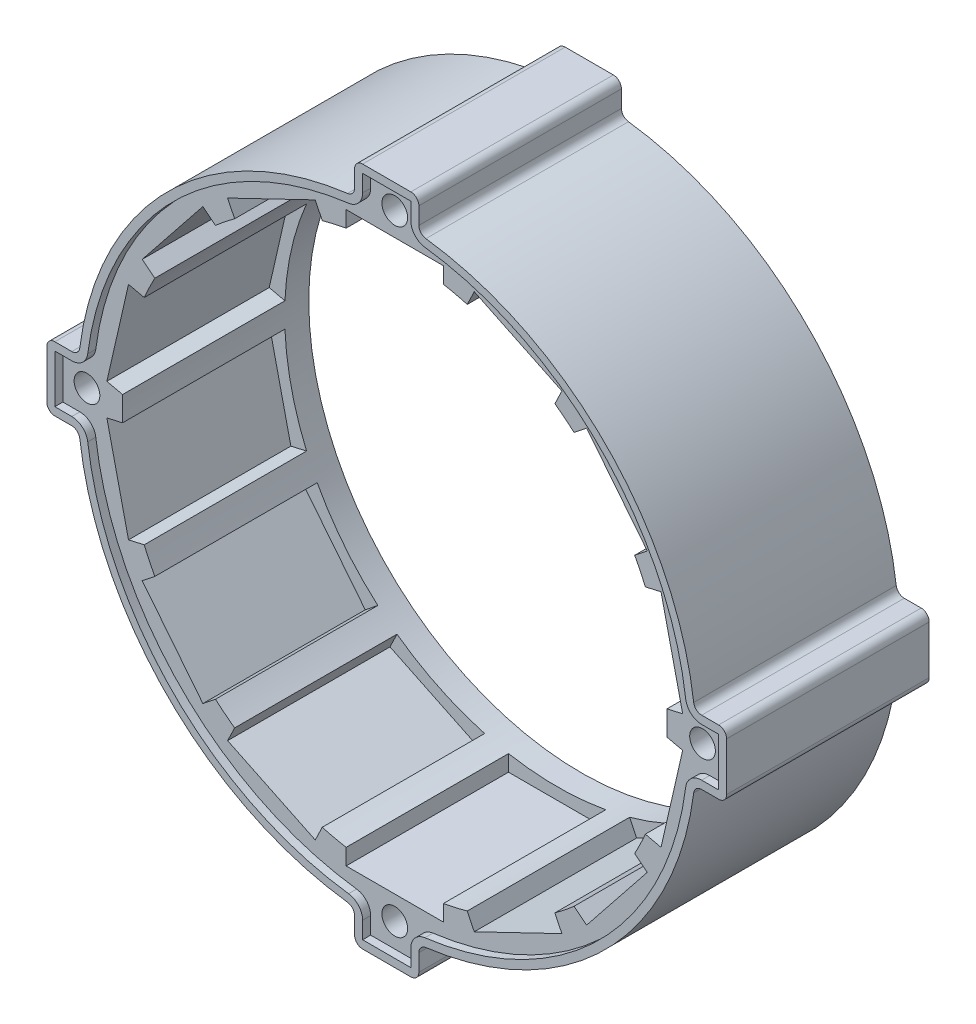
SolidWorks part; units mm, degrees
ref_plane "正面" through (0, 0, 0) normal (0, 0, 1) x (1, 0, 0)
ref_plane "平面" through (0, 0, 0) normal (0, 1, 0) x (1, 0, 0)
ref_plane "右側面" through (0, 0, 0) normal (1, 0, 0) x (0, 0, -1)
sketch "ｽｹｯﾁ1" plane through (0, 0, 0) normal (0, 0, 1) x (1, 0, 0)
  line L0 (38.8333, 0) -> (34.9876, 16.8491) construction
  line L1 (33.7047, 0) -> (30.3669, 14.6239)
  line L2 (30.3669, 14.6239) -> (21.0145, 26.3514)
  line L3 (21.0145, 26.3514) -> (7.5, 32.8596)
  line L4 (7.5, 32.8596) -> (-7.5, 32.8596)
  line L5 (-7.5, 32.8596) -> (-21.0145, 26.3514)
  line L6 (-21.0145, 26.3514) -> (-30.3669, 14.6239)
  line L7 (-30.3669, 14.6239) -> (-33.7047, 0)
  line L8 (-33.7047, 0) -> (-30.3669, -14.6239)
  line L9 (-30.3669, -14.6239) -> (-21.0145, -26.3514)
  line L10 (-21.0145, -26.3514) -> (-7.5, -32.8596)
  line L11 (-7.5, -32.8596) -> (7.5, -32.8596)
  line L12 (7.5, -32.8596) -> (21.0145, -26.3514)
  line L13 (21.0145, -26.3514) -> (30.3669, -14.6239)
  line L14 (30.3669, -14.6239) -> (33.7047, 0)
  line L15 (34.9876, 16.8491) -> (24.2122, 30.3611) construction
  line L16 (24.2122, 30.3611) -> (8.6412, 37.8596) construction
  line L17 (8.6412, 37.8596) -> (-8.6412, 37.8596) construction
  line L18 (-8.6412, 37.8596) -> (-24.2122, 30.3611) construction
  line L19 (-24.2122, 30.3611) -> (-34.9876, 16.8491) construction
  line L20 (-34.9876, 16.8491) -> (-38.8333, 0) construction
  line L21 (-38.8333, 0) -> (-34.9876, -16.8491) construction
  line L22 (-34.9876, -16.8491) -> (-24.2122, -30.3611) construction
  line L23 (-24.2122, -30.3611) -> (-8.6412, -37.8596) construction
  line L24 (-8.6412, -37.8596) -> (8.6412, -37.8596) construction
  line L25 (8.6412, -37.8596) -> (24.2122, -30.3611) construction
  line L26 (24.2122, -30.3611) -> (34.9876, -16.8491) construction
  line L27 (34.9876, -16.8491) -> (38.8333, 0) construction
  circle A0 centre (0, 0) radius 32.8596 construction
  circle A1 centre (0, 0) radius 38.5
  dimension "D3" = 77
  dimension "D1" = 15
  dimension "D2" = 5
extrude "ﾎﾞｽ - 押し出し1" add sketch "ｽｹｯﾁ1" along normal blind 20.2
ref_axis "軸1" through (0, 0, 0) along (0, 0, 1)
sketch "ｽｹｯﾁ3" plane through (0, 0, 20.2) normal (0, 0, 1) x (1, 0, 0)
  line L0 (0, 0) -> (0, 33.0954) construction
  line L1 (7.5, 32.8596) -> (-7.5, 32.8596) construction
  line L2 (-6.05, 35.3596) -> (6.05, 35.3596)
  line L3 (-6.05, 35.3596) -> (-6.05, 32.8596)
  line L4 (-6.05, 32.8596) -> (6.05, 32.8596)
  line L5 (6.05, 35.3596) -> (6.05, 32.8596)
  line L6 (-6.05, 35.3596) -> (6.05, 32.8596) construction
  line L7 (-6.05, 32.8596) -> (6.05, 35.3596) construction
  point P3 (0, 34.1096)
  dimension "D1" = 2.5
  dimension "D2" = 12.1
extrude "ｶｯﾄ - 押し出し2" cut sketch "ｽｹｯﾁ3" against normal through all
pattern_circular "円形ﾊﾟﾀｰﾝ2" count 14 over 360 about axis through (0, 0, 0) along (0, 0, 1) of "ｶｯﾄ - 押し出し2"
sketch "ｽｹｯﾁ5" plane through (0, 0, 0) normal (0, 0, -1) x (-1, 0, 0)
  circle A0 centre (0, 0) radius 33.9
  circle A1 centre (0, 0) radius 38.5
  circle A2 centre (0, 0) radius 38.5
  dimension "D1" = 0
  dimension "D2" = 4.6
extrude "ﾎﾞｽ - 押し出し2" add sketch "ｽｹｯﾁ5" along normal blind 3
sketch "ｽｹｯﾁ6" plane through (0, 0, -3) normal (0, 0, -1) x (-1, 0, 0)
  circle A0 centre (0, 0) radius 33.9 construction
  circle A1 centre (0, 0) radius 33.9
extrude "ｶｯﾄ - 押し出し3" cut sketch "ｽｹｯﾁ6" against normal through all
sketch "ｽｹｯﾁ7" plane through (0, 0, -3) normal (0, 0, -1) x (-1, 0, 0)
  line L0 (0, 0) -> (0, 38.5) construction
  line L1 (4, 42.2916) -> (-4, 42.2916)
  line L2 (-4, 42.2916) -> (-4, 38.2916)
  line L3 (4, 42.2916) -> (4, 38.2916)
  circle A0 centre (0, 0) radius 38.5 construction
  circle A2 centre (0, 0) radius 38.5
  arc A3 (4, 38.2916) -> (-4, 38.2916) centre (0, 0) ccw
  point P10 (0, 42.2916)
  dimension "D2" = 8
  dimension "D3" = 4
  dimension "D1" = 0
extrude "ﾎﾞｽ - 押し出し3" add sketch "ｽｹｯﾁ7" against normal up to surface (23.2 mm away) up to face at (0, 0, 20.2)
pattern_circular "円形ﾊﾟﾀｰﾝ3" count 4 over 360 about axis through (0, 0, 0) along (0, 0, 1) of "ﾎﾞｽ - 押し出し3"
sketch "ｽｹｯﾁ8" plane through (0, 0, -3) normal (0, 0, -1) x (-1, 0, 0)
  line L0 (4, 42.2916) -> (-4, 42.2916) construction
  line L1 (0, 0) -> (0, 38.2916) construction
  circle A0 centre (0, 38.2916) radius 1.6
  circle A4 centre (38.2916, 0) radius 1.6
  circle A5 centre (0, -38.2916) radius 1.6
  circle A6 centre (-38.2916, 0) radius 1.6
  point P13 (-0.4544, 0.4544)
  point P15 (0, 0)
  dimension "D1" = 3.2
  dimension "D2" = 4
  dimension "D3" = 4
extrude "ｶｯﾄ - 押し出し4" cut sketch "ｽｹｯﾁ8" against normal through all
fillet "ﾌｨﾚｯﾄ1" radius 1 16 edges at (4, -38.2916, 8.6) (4, -42.2916, 8.6) (-4, -42.2916, 8.6) (-4, -38.2916, 8.6) (-38.2916, -4, 8.6) (-42.2916, -4, 8.6) (-42.2916, 4, 8.6) (-38.2916, 4, 8.6) (-4, 38.2916, 8.6) (-4, 42.2916, 8.6) (4, 42.2916, 8.6) (4, 38.2916, 8.6) (38.2916, 4, 8.6) (42.2916, 4, 8.6) (42.2916, -4, 8.6) (38.2916, -4, 8.6)
sketch "ｽｹｯﾁ9" plane through (0, 0, -3) normal (0, 0, -1) x (-1, 0, 0)
  line L0 (-3, -39.1823) -> (-3, -41.2916)
  line L1 (-3, -41.2916) -> (3, -41.2916)
  line L2 (3, -41.2916) -> (3, -39.1823)
  line L3 (39.1823, -3) -> (41.2916, -3)
  line L4 (41.2916, -3) -> (41.2916, 3)
  line L5 (41.2916, 3) -> (39.1823, 3)
  line L6 (3, 39.1823) -> (3, 41.2916)
  line L7 (3, 41.2916) -> (-3, 41.2916)
  line L8 (-3, 41.2916) -> (-3, 39.1823)
  line L9 (-39.1823, 3) -> (-41.2916, 3)
  line L10 (-41.2916, 3) -> (-41.2916, -3)
  line L11 (-41.2916, -3) -> (-39.1823, -3)
  line L12 (-4, -39.1823) -> (-4, -41.2916)
  line L13 (-3, -42.2916) -> (3, -42.2916)
  line L14 (4, -41.2916) -> (4, -39.1823)
  line L15 (39.1823, -4) -> (41.2916, -4)
  line L16 (42.2916, -3) -> (42.2916, 3)
  line L17 (41.2916, 4) -> (39.1823, 4)
  line L18 (4, 39.1823) -> (4, 41.2916)
  line L19 (3, 42.2916) -> (-3, 42.2916)
  line L20 (-4, 41.2916) -> (-4, 39.1823)
  line L21 (-39.1823, 4) -> (-41.2916, 4)
  line L22 (-42.2916, 3) -> (-42.2916, -3)
  line L23 (-41.2916, -4) -> (-39.1823, -4)
  line L24 (-4, -39.1823) -> (-4, -41.2916)
  line L25 (-3, -42.2916) -> (3, -42.2916)
  line L26 (4, -41.2916) -> (4, -39.1823)
  line L27 (39.1823, -4) -> (41.2916, -4)
  line L28 (42.2916, -3) -> (42.2916, 3)
  line L29 (41.2916, 4) -> (39.1823, 4)
  line L30 (4, 39.1823) -> (4, 41.2916)
  line L31 (3, 42.2916) -> (-3, 42.2916)
  line L32 (-4, 41.2916) -> (-4, 39.1823)
  line L33 (-39.1823, 4) -> (-41.2916, 4)
  line L34 (-42.2916, 3) -> (-42.2916, -3)
  line L35 (-41.2916, -4) -> (-39.1823, -4)
  arc A0 (-3, -41.2916) -> (-3, -41.2916) centre (-3, -41.2916) ccw
  arc A1 (3, -41.2916) -> (3, -41.2916) centre (3, -41.2916) ccw
  arc A2 (4.7468, -37.1984) -> (3, -39.1823) centre (5, -39.1823) ccw
  arc A3 (4.7468, -37.1984) -> (37.1984, -4.7468) centre (0, 0) ccw
  arc A4 (39.1823, -3) -> (37.1984, -4.7468) centre (39.1823, -5) ccw
  arc A5 (41.2916, -3) -> (41.2916, -3) centre (41.2916, -3) ccw
  arc A6 (41.2916, 3) -> (41.2916, 3) centre (41.2916, 3) ccw
  arc A7 (37.1984, 4.7468) -> (39.1823, 3) centre (39.1823, 5) ccw
  arc A8 (37.1984, 4.7468) -> (4.7468, 37.1984) centre (0, 0) ccw
  arc A9 (3, 39.1823) -> (4.7468, 37.1984) centre (5, 39.1823) ccw
  arc A10 (3, 41.2916) -> (3, 41.2916) centre (3, 41.2916) ccw
  arc A11 (-3, 41.2916) -> (-3, 41.2916) centre (-3, 41.2916) ccw
  arc A12 (-4.7468, 37.1984) -> (-3, 39.1823) centre (-5, 39.1823) ccw
  arc A13 (-4.7468, 37.1984) -> (-37.1984, 4.7468) centre (0, 0) ccw
  arc A14 (-39.1823, 3) -> (-37.1984, 4.7468) centre (-39.1823, 5) ccw
  arc A15 (-41.2916, 3) -> (-41.2916, 3) centre (-41.2916, 3) ccw
  arc A16 (-41.2916, -3) -> (-41.2916, -3) centre (-41.2916, -3) ccw
  arc A17 (-37.1984, -4.7468) -> (-39.1823, -3) centre (-39.1823, -5) ccw
  arc A18 (-37.1984, -4.7468) -> (-4.7468, -37.1984) centre (0, 0) ccw
  arc A19 (-3, -39.1823) -> (-4.7468, -37.1984) centre (-5, -39.1823) ccw
  arc A20 (-4, -41.2916) -> (-3, -42.2916) centre (-3, -41.2916) ccw
  arc A21 (3, -42.2916) -> (4, -41.2916) centre (3, -41.2916) ccw
  arc A22 (4.8734, -38.1903) -> (4, -39.1823) centre (5, -39.1823) ccw
  arc A23 (4.8734, -38.1903) -> (38.1903, -4.8734) centre (0, 0) ccw
  arc A24 (39.1823, -4) -> (38.1903, -4.8734) centre (39.1823, -5) ccw
  arc A25 (41.2916, -4) -> (42.2916, -3) centre (41.2916, -3) ccw
  arc A26 (42.2916, 3) -> (41.2916, 4) centre (41.2916, 3) ccw
  arc A27 (38.1903, 4.8734) -> (39.1823, 4) centre (39.1823, 5) ccw
  arc A28 (38.1903, 4.8734) -> (4.8734, 38.1903) centre (0, 0) ccw
  arc A29 (4, 39.1823) -> (4.8734, 38.1903) centre (5, 39.1823) ccw
  arc A30 (4, 41.2916) -> (3, 42.2916) centre (3, 41.2916) ccw
  arc A31 (-3, 42.2916) -> (-4, 41.2916) centre (-3, 41.2916) ccw
  arc A32 (-4.8734, 38.1903) -> (-4, 39.1823) centre (-5, 39.1823) ccw
  arc A33 (-4.8734, 38.1903) -> (-38.1903, 4.8734) centre (0, 0) ccw
  arc A34 (-39.1823, 4) -> (-38.1903, 4.8734) centre (-39.1823, 5) ccw
  arc A35 (-41.2916, 4) -> (-42.2916, 3) centre (-41.2916, 3) ccw
  arc A36 (-42.2916, -3) -> (-41.2916, -4) centre (-41.2916, -3) ccw
  arc A37 (-38.1903, -4.8734) -> (-39.1823, -4) centre (-39.1823, -5) ccw
  arc A38 (-38.1903, -4.8734) -> (-4.8734, -38.1903) centre (0, 0) ccw
  arc A39 (-4, -39.1823) -> (-4.8734, -38.1903) centre (-5, -39.1823) ccw
  arc A40 (-4, -41.2916) -> (-3, -42.2916) centre (-3, -41.2916) ccw
  arc A41 (3, -42.2916) -> (4, -41.2916) centre (3, -41.2916) ccw
  arc A42 (4.8734, -38.1903) -> (4, -39.1823) centre (5, -39.1823) ccw
  arc A43 (4.8734, -38.1903) -> (38.1903, -4.8734) centre (0, 0) ccw
  arc A44 (39.1823, -4) -> (38.1903, -4.8734) centre (39.1823, -5) ccw
  arc A45 (41.2916, -4) -> (42.2916, -3) centre (41.2916, -3) ccw
  arc A46 (42.2916, 3) -> (41.2916, 4) centre (41.2916, 3) ccw
  arc A47 (38.1903, 4.8734) -> (39.1823, 4) centre (39.1823, 5) ccw
  arc A48 (38.1903, 4.8734) -> (4.8734, 38.1903) centre (0, 0) ccw
  arc A49 (4, 39.1823) -> (4.8734, 38.1903) centre (5, 39.1823) ccw
  arc A50 (4, 41.2916) -> (3, 42.2916) centre (3, 41.2916) ccw
  arc A51 (-3, 42.2916) -> (-4, 41.2916) centre (-3, 41.2916) ccw
  arc A52 (-4.8734, 38.1903) -> (-4, 39.1823) centre (-5, 39.1823) ccw
  arc A53 (-4.8734, 38.1903) -> (-38.1903, 4.8734) centre (0, 0) ccw
  arc A54 (-39.1823, 4) -> (-38.1903, 4.8734) centre (-39.1823, 5) ccw
  arc A55 (-41.2916, 4) -> (-42.2916, 3) centre (-41.2916, 3) ccw
  arc A56 (-42.2916, -3) -> (-41.2916, -4) centre (-41.2916, -3) ccw
  arc A57 (-38.1903, -4.8734) -> (-39.1823, -4) centre (-39.1823, -5) ccw
  arc A58 (-38.1903, -4.8734) -> (-4.8734, -38.1903) centre (0, 0) ccw
  arc A59 (-4, -39.1823) -> (-4.8734, -38.1903) centre (-5, -39.1823) ccw
  dimension "D1" = 0
  dimension "D2" = 1
extrude "ﾎﾞｽ - 押し出し4" add sketch "ｽｹｯﾁ9" along normal blind 1
sketch "ｽｹｯﾁ10" plane through (0, 0, 20.2) normal (0, 0, 1) x (1, 0, 0)
  line L0 (-3, -41.2916) -> (3, -41.2916)
  line L1 (3, -41.2916) -> (3, -39.1823)
  line L2 (39.1823, -3) -> (41.2916, -3)
  line L3 (41.2916, -3) -> (41.2916, 3)
  line L4 (41.2916, 3) -> (39.1823, 3)
  line L5 (3, 39.1823) -> (3, 41.2916)
  line L6 (3, 41.2916) -> (-3, 41.2916)
  line L7 (-3, 41.2916) -> (-3, 39.1823)
  line L8 (-39.1823, 3) -> (-41.2916, 3)
  line L9 (-41.2916, 3) -> (-41.2916, -3)
  line L10 (-41.2916, -3) -> (-39.1823, -3)
  line L11 (-3, -39.1823) -> (-3, -41.2916)
  line L12 (-3, -42.2916) -> (3, -42.2916)
  line L13 (4, -41.2916) -> (4, -39.1823)
  line L14 (39.1823, -4) -> (41.2916, -4)
  line L15 (42.2916, -3) -> (42.2916, 3)
  line L16 (41.2916, 4) -> (39.1823, 4)
  line L17 (4, 39.1823) -> (4, 41.2916)
  line L18 (3, 42.2916) -> (-3, 42.2916)
  line L19 (-4, 41.2916) -> (-4, 39.1823)
  line L20 (-39.1823, 4) -> (-41.2916, 4)
  line L21 (-42.2916, 3) -> (-42.2916, -3)
  line L22 (-41.2916, -4) -> (-39.1823, -4)
  line L23 (-4, -39.1823) -> (-4, -41.2916)
  line L24 (-3, -42.2916) -> (3, -42.2916)
  line L25 (4, -41.2916) -> (4, -39.1823)
  line L26 (39.1823, -4) -> (41.2916, -4)
  line L27 (42.2916, -3) -> (42.2916, 3)
  line L28 (41.2916, 4) -> (39.1823, 4)
  line L29 (4, 39.1823) -> (4, 41.2916)
  line L30 (3, 42.2916) -> (-3, 42.2916)
  line L31 (-4, 41.2916) -> (-4, 39.1823)
  line L32 (-39.1823, 4) -> (-41.2916, 4)
  line L33 (-42.2916, 3) -> (-42.2916, -3)
  line L34 (-41.2916, -4) -> (-39.1823, -4)
  line L35 (-4, -39.1823) -> (-4, -41.2916)
  arc A0 (3, -41.2916) -> (3, -41.2916) centre (3, -41.2916) ccw
  arc A1 (4.7468, -37.1984) -> (3, -39.1823) centre (5, -39.1823) ccw
  arc A2 (4.7468, -37.1984) -> (37.1984, -4.7468) centre (0, 0) ccw
  arc A3 (39.1823, -3) -> (37.1984, -4.7468) centre (39.1823, -5) ccw
  arc A4 (41.2916, -3) -> (41.2916, -3) centre (41.2916, -3) ccw
  arc A5 (41.2916, 3) -> (41.2916, 3) centre (41.2916, 3) ccw
  arc A6 (37.1984, 4.7468) -> (39.1823, 3) centre (39.1823, 5) ccw
  arc A7 (37.1984, 4.7468) -> (4.7468, 37.1984) centre (0, 0) ccw
  arc A8 (3, 39.1823) -> (4.7468, 37.1984) centre (5, 39.1823) ccw
  arc A9 (3, 41.2916) -> (3, 41.2916) centre (3, 41.2916) ccw
  arc A10 (-3, 41.2916) -> (-3, 41.2916) centre (-3, 41.2916) ccw
  arc A11 (-4.7468, 37.1984) -> (-3, 39.1823) centre (-5, 39.1823) ccw
  arc A12 (-4.7468, 37.1984) -> (-37.1984, 4.7468) centre (0, 0) ccw
  arc A13 (-39.1823, 3) -> (-37.1984, 4.7468) centre (-39.1823, 5) ccw
  arc A14 (-41.2916, 3) -> (-41.2916, 3) centre (-41.2916, 3) ccw
  arc A15 (-41.2916, -3) -> (-41.2916, -3) centre (-41.2916, -3) ccw
  arc A16 (-37.1984, -4.7468) -> (-39.1823, -3) centre (-39.1823, -5) ccw
  arc A17 (-37.1984, -4.7468) -> (-4.7468, -37.1984) centre (0, 0) ccw
  arc A18 (-3, -39.1823) -> (-4.7468, -37.1984) centre (-5, -39.1823) ccw
  arc A19 (-3, -41.2916) -> (-3, -41.2916) centre (-3, -41.2916) ccw
  arc A20 (3, -42.2916) -> (4, -41.2916) centre (3, -41.2916) ccw
  arc A21 (4.8734, -38.1903) -> (4, -39.1823) centre (5, -39.1823) ccw
  arc A22 (4.8734, -38.1903) -> (38.1903, -4.8734) centre (0, 0) ccw
  arc A23 (39.1823, -4) -> (38.1903, -4.8734) centre (39.1823, -5) ccw
  arc A24 (41.2916, -4) -> (42.2916, -3) centre (41.2916, -3) ccw
  arc A25 (42.2916, 3) -> (41.2916, 4) centre (41.2916, 3) ccw
  arc A26 (38.1903, 4.8734) -> (39.1823, 4) centre (39.1823, 5) ccw
  arc A27 (38.1903, 4.8734) -> (4.8734, 38.1903) centre (0, 0) ccw
  arc A28 (4, 39.1823) -> (4.8734, 38.1903) centre (5, 39.1823) ccw
  arc A29 (4, 41.2916) -> (3, 42.2916) centre (3, 41.2916) ccw
  arc A30 (-3, 42.2916) -> (-4, 41.2916) centre (-3, 41.2916) ccw
  arc A31 (-4.8734, 38.1903) -> (-4, 39.1823) centre (-5, 39.1823) ccw
  arc A32 (-4.8734, 38.1903) -> (-38.1903, 4.8734) centre (0, 0) ccw
  arc A33 (-39.1823, 4) -> (-38.1903, 4.8734) centre (-39.1823, 5) ccw
  arc A34 (-41.2916, 4) -> (-42.2916, 3) centre (-41.2916, 3) ccw
  arc A35 (-42.2916, -3) -> (-41.2916, -4) centre (-41.2916, -3) ccw
  arc A36 (-38.1903, -4.8734) -> (-39.1823, -4) centre (-39.1823, -5) ccw
  arc A37 (-38.1903, -4.8734) -> (-4.8734, -38.1903) centre (0, 0) ccw
  arc A38 (-4, -39.1823) -> (-4.8734, -38.1903) centre (-5, -39.1823) ccw
  arc A39 (-4, -41.2916) -> (-3, -42.2916) centre (-3, -41.2916) ccw
  arc A40 (3, -42.2916) -> (4, -41.2916) centre (3, -41.2916) ccw
  arc A41 (4.8734, -38.1903) -> (4, -39.1823) centre (5, -39.1823) ccw
  arc A42 (4.8734, -38.1903) -> (38.1903, -4.8734) centre (0, 0) ccw
  arc A43 (39.1823, -4) -> (38.1903, -4.8734) centre (39.1823, -5) ccw
  arc A44 (41.2916, -4) -> (42.2916, -3) centre (41.2916, -3) ccw
  arc A45 (42.2916, 3) -> (41.2916, 4) centre (41.2916, 3) ccw
  arc A46 (38.1903, 4.8734) -> (39.1823, 4) centre (39.1823, 5) ccw
  arc A47 (38.1903, 4.8734) -> (4.8734, 38.1903) centre (0, 0) ccw
  arc A48 (4, 39.1823) -> (4.8734, 38.1903) centre (5, 39.1823) ccw
  arc A49 (4, 41.2916) -> (3, 42.2916) centre (3, 41.2916) ccw
  arc A50 (-3, 42.2916) -> (-4, 41.2916) centre (-3, 41.2916) ccw
  arc A51 (-4.8734, 38.1903) -> (-4, 39.1823) centre (-5, 39.1823) ccw
  arc A52 (-4.8734, 38.1903) -> (-38.1903, 4.8734) centre (0, 0) ccw
  arc A53 (-39.1823, 4) -> (-38.1903, 4.8734) centre (-39.1823, 5) ccw
  arc A54 (-41.2916, 4) -> (-42.2916, 3) centre (-41.2916, 3) ccw
  arc A55 (-42.2916, -3) -> (-41.2916, -4) centre (-41.2916, -3) ccw
  arc A56 (-38.1903, -4.8734) -> (-39.1823, -4) centre (-39.1823, -5) ccw
  arc A57 (-38.1903, -4.8734) -> (-4.8734, -38.1903) centre (0, 0) ccw
  arc A58 (-4, -39.1823) -> (-4.8734, -38.1903) centre (-5, -39.1823) ccw
  arc A59 (-4, -41.2916) -> (-3, -42.2916) centre (-3, -41.2916) ccw
  dimension "D1" = 0
  dimension "D2" = 1
extrude "ﾎﾞｽ - 押し出し6" add sketch "ｽｹｯﾁ10" along normal blind 1
